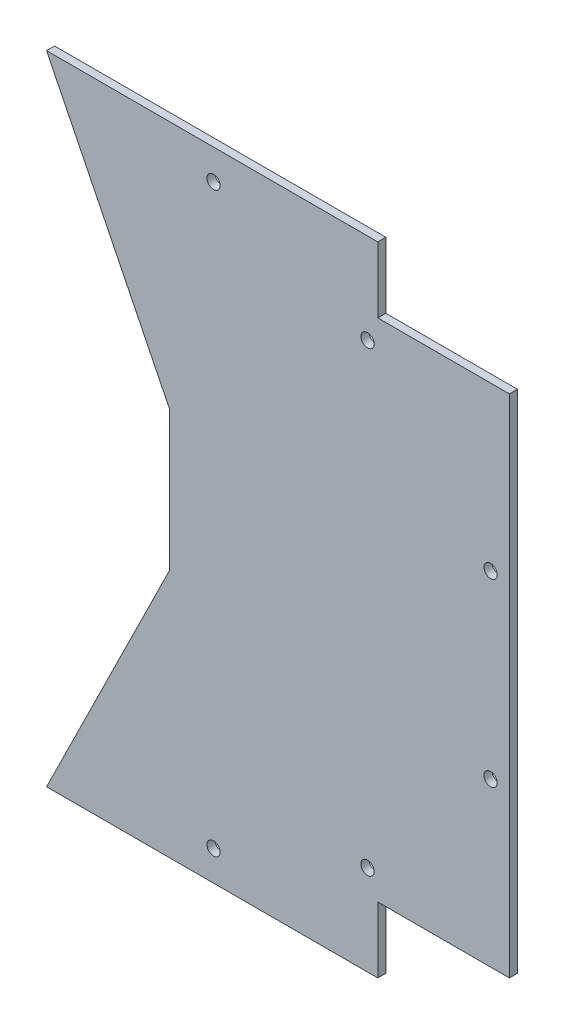
SolidWorks part; units mm, degrees
material "Thornel Mat VMA"
ref_plane "Front Plane" through (0, 0, 0) normal (0, 0, 1) x (1, 0, 0)
ref_plane "Top Plane" through (0, 0, 0) normal (0, 1, 0) x (1, 0, 0)
ref_plane "Right Plane" through (0, 0, 0) normal (1, 0, 0) x (0, 0, -1)
sketch "Sketch2" plane through (0, 0, 0) normal (0, 0, 1) x (-1, 0, 0)
  line L11 (-2.9301, 168.7083) -> (38.7094, 168.7083)
  line L12 (-2.9301, 8.6883) -> (38.7094, 8.6883)
  line L13 (38.7094, -12.1397) -> (38.7094, 8.6883)
  line L14 (143.4971, -12.1397) -> (38.7094, -12.1397)
  line L15 (38.7094, 189.5363) -> (38.7094, 168.7083)
  line L16 (143.4971, 189.5363) -> (38.7094, 189.5363)
  line L17 (104.6174, 110.8598) -> (143.4971, 189.5363)
  line L18 (104.6174, 66.5368) -> (143.4971, -12.1397)
  line L19 (104.6174, 66.5368) -> (72.8674, 66.5368)
  line L20 (72.8674, 66.5368) -> (72.8674, 110.8598)
  line L21 (104.6174, 110.8598) -> (72.8674, 110.8598)
  line L22 (-2.9301, 168.7083) -> (-2.9301, 8.6883)
  line L23 (41.9566, 19.6103) -> (41.9566, 13.2603) construction
  circle A0 centre (41.9566, 160.9613) radius 2.0955
  circle A1 centre (90.6739, 180.0113) radius 2.0955
  circle A2 centre (90.6739, -2.6147) radius 2.0955
  circle A3 centre (3.0351, 117.2098) radius 2.0955
  circle A4 centre (3.0351, 60.1868) radius 2.0955
  circle A5 centre (41.9566, 16.4353) radius 2.0955
  point P36 (41.9566, 16.4353)
  dimension "D1" = 4.191
  dimension "D2" = 4.191
  dimension "D3" = 4.191
  dimension "D4" = 4.191
  dimension "D5" = 4.191
  dimension "D6" = 4.191
  dimension "D7" = 31.75
  dimension "D8" = 41.6395
  dimension "D9" = 20.828
  dimension "D10" = 160.02
  dimension "D11" = 20.828
  dimension "D12" = 41.6395
  dimension "D13" = 104.7876
  dimension "D14" = 116.297
  dimension "D15" = 116.297
  dimension "D16" = 44.323
  dimension "D17" = 26.297
  dimension "D18" = 9.525
  dimension "D19" = 28.575
  dimension "D20" = 7.747
  dimension "D21" = 51.9645
  dimension "D22" = 51.4985
  dimension "D23" = 5.9651
  dimension "D24" = 51.4985
  dimension "D25" = 5.9651
  dimension "D26" = 7.747
  dimension "D27" = 3.2471
  dimension "D28" = 9.525
  dimension "D29" = 51.9645
extrude "Boss-Extrude1" add sketch "Sketch2" along normal blind 2.54
sketch "Sketch3" plane through (0, 0, 2.54) normal (0, 0, 1) x (1, 0, 0)
  line L1 (-104.6174, -66.5368) -> (-72.8674, -66.5368)
  line L2 (-104.6174, -66.5368) -> (-104.6174, -110.8598)
  line L3 (-104.6174, -110.8598) -> (-72.8674, -110.8598)
  line L4 (-72.8674, -66.5368) -> (-72.8674, -110.8598)
extrude "Boss-Extrude2" add sketch "Sketch3" against normal up to surface (2.54 mm away) up to face at (-65.9118, -88.6983, 0)
